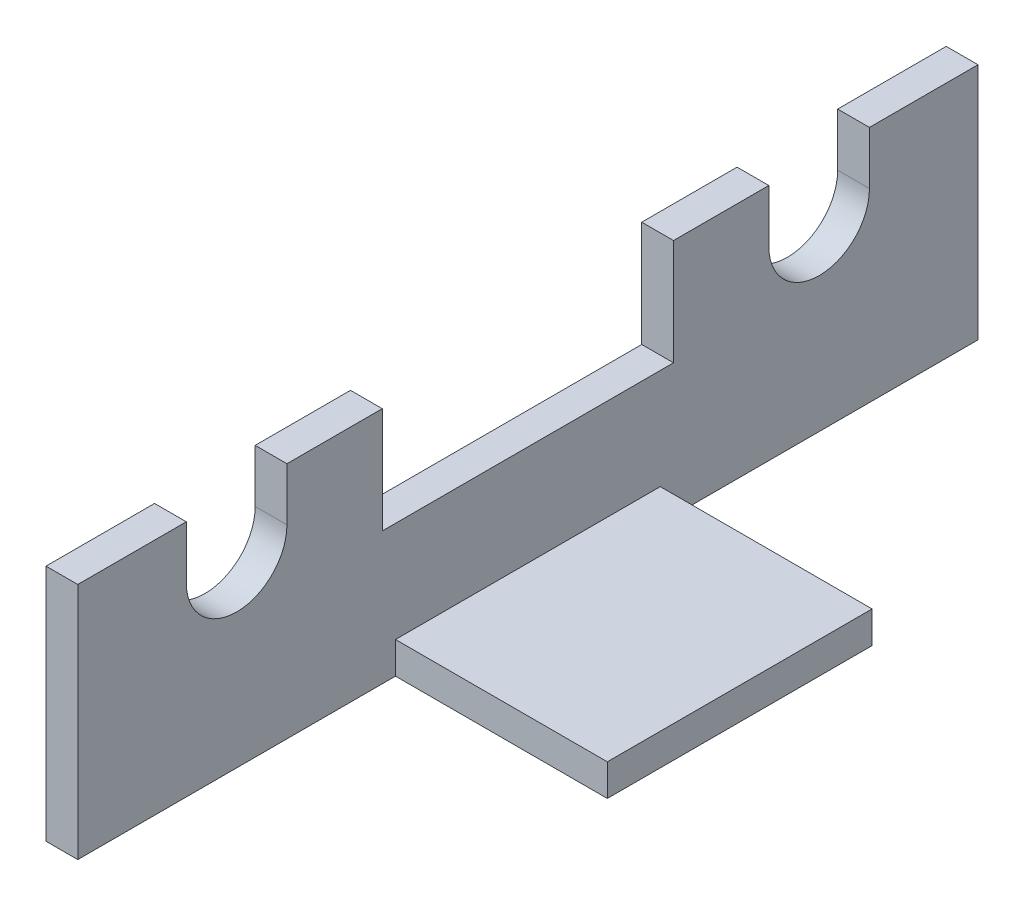
SolidWorks part; units mm, degrees
ref_plane "Alzado" through (0, 0, 0) normal (0, 0, 1) x (1, 0, 0)
ref_plane "Planta" through (0, 0, 0) normal (0, 1, 0) x (1, 0, 0)
ref_plane "Vista lateral" through (0, 0, 0) normal (1, 0, 0) x (0, 0, -1)
sketch "Croquis1" plane through (0, 0, 0) normal (0, 0, 1) x (1, 0, 0)
  line L0 (0, 0) -> (0, 50)
  line L1 (0, 0) -> (50, 0)
  line L2 (6, 6) -> (50, 6)
  line L3 (6, 6) -> (6, 50)
  line L4 (0, 50) -> (6, 50)
  line L5 (50, 6) -> (50, 0)
  dimension "D2" = 50
  dimension "D1" = 6
extrude "Saliente-Extruir1" add sketch "Croquis1" along normal blind 170
sketch "Croquis2" plane through (0, 0, 0) normal (-1, 0, 0) x (0, 0, 1)
  line L0 (170, 35) -> (0, 35) construction
  line L1 (170, 50) -> (170, 0) construction
  line L2 (0, 50) -> (0, 0) construction
  line L3 (170, 6) -> (0, 6) construction
  line L4 (170, 6) -> (0, 6) construction
  line L5 (85, 6) -> (85, 50) construction
  line L6 (170, 50) -> (0, 50) construction
  line L7 (112.5, 25) -> (112.5, 50)
  line L8 (112.5, 75) -> (57.5, 75) construction
  line L9 (112.5, 75) -> (112.5, 25) construction
  line L10 (112.5, 25) -> (57.5, 25)
  line L11 (57.5, 75) -> (57.5, 25) construction
  line L12 (112.5, 75) -> (57.5, 25) construction
  line L13 (112.5, 25) -> (57.5, 75) construction
  line L14 (57.5, 25) -> (57.5, 50)
  line L15 (57.5, 50) -> (112.5, 50)
  line L16 (149.5, 35) -> (149.5, 50)
  line L17 (130.5, 35) -> (130.5, 50)
  line L18 (130.5, 50) -> (149.5, 50)
  line L19 (39.5, 35) -> (39.5, 50)
  line L20 (20.5, 35) -> (20.5, 50)
  line L21 (39.5, 50) -> (20.5, 50)
  line L22 (170, 0) -> (0, 0) construction
  circle A0 centre (140, 35) radius 9.5 construction
  circle A1 centre (30, 35) radius 9.5 construction
  arc A2 (149.5, 35) -> (130.5, 35) centre (140, 35) cw
  arc A3 (39.5, 35) -> (20.5, 35) centre (30, 35) cw
  dimension "D2" = 19
  dimension "D1" = 35
  dimension "D3" = 55
  dimension "D4" = 55
  dimension "D5" = 25
  dimension "D6" = 55
  dimension "D7" = 20.5
  dimension "D8" = 20.5
extrude "Cortar-Extruir1" cut sketch "Croquis2" against normal up to surface (6 mm away) up to face at (6, 28, 85)
sketch "Croquis3" plane through (0, 0, 0) normal (0, -1, 0) x (1, 0, 0)
  line L0 (0, 85) -> (50, 85) construction
  line L1 (0, 170) -> (0, 0) construction
  line L2 (50, 170) -> (50, 0) construction
  line L3 (6, 170) -> (6, 0) construction
  line L4 (50, 0) -> (6, 0)
  line L5 (50, 0) -> (50, 60)
  line L6 (50, 60) -> (6, 60)
  line L7 (6, 0) -> (6, 60)
  line L8 (6, 170) -> (6, 0) construction
  line L9 (50, 110) -> (6, 110)
  line L10 (6, 170) -> (6, 110)
  line L11 (50, 170) -> (6, 170)
  line L12 (50, 170) -> (50, 110)
  line M5 (0, 0) -> (50, 0)
  line M6 (50, 0) -> (50, 170)
  line M7 (50, 170) -> (0, 170)
  dimension "D1" = 60
extrude "Cortar-Extruir2" cut sketch "Croquis3" against normal up to surface (6 mm away) contours L10 L9 M7 M6 | L7 L6 M5 M6 region at (28, 0, 140) region at (28, 0, 30) up to face at (28, 6, 85)
sketch "Croquis4" plane through (0, 0, 0) normal (0, -1, 0) x (1, 0, 0)
  line L0 (46, 60) -> (46, 110)
  line L1 (50, 60) -> (6, 60) construction
  line L2 (50, 110) -> (6, 110) construction
  line L3 (46, 110) -> (50, 110)
  line L4 (50, 110) -> (50, 60)
  line L5 (50, 60) -> (46, 60)
  dimension "D1" = 4
extrude "Cortar-Extruir3" cut sketch "Croquis4" against normal blind 10
sketch "Croquis5" plane through (0, 0, 0) normal (-1, 0, 0) x (0, 0, 1)
  line L0 (170, 45) -> (0, 45) construction
  line L1 (170, 50) -> (170, 0) construction
  line L2 (0, 50) -> (0, 0) construction
  line L3 (170, 50) -> (149.5, 50) construction
  line L4 (170, 45) -> (149.5, 45)
  line L5 (149.5, 45) -> (149.5, 50)
  line L6 (149.5, 50) -> (170, 50)
  line L7 (170, 50) -> (170, 45)
  line L8 (149.5, 35) -> (149.5, 50) construction
  line L9 (112.5, 50) -> (112.5, 45)
  line L10 (112.5, 25) -> (112.5, 50) construction
  line L11 (112.5, 45) -> (130.5, 45)
  line L12 (130.5, 50) -> (130.5, 35) construction
  line L13 (130.5, 45) -> (130.5, 50)
  line L14 (130.5, 50) -> (112.5, 50)
  line L15 (85, 25) -> (85, 45) construction
  line L16 (57.5, 25) -> (112.5, 25) construction
  line L17 (39.5, 45) -> (39.5, 50)
  line L18 (57.5, 45) -> (39.5, 45)
  line L19 (57.5, 50) -> (57.5, 45)
  line L20 (39.5, 50) -> (57.5, 50)
  line L21 (20.5, 50) -> (0, 50)
  line L22 (20.5, 45) -> (20.5, 50)
  line L23 (0, 45) -> (20.5, 45)
  line L24 (0, 50) -> (0, 45)
  dimension "D1" = 5
extrude "Cortar-Extruir4" cut sketch "Croquis5" against normal up to surface (6 mm away) up to face at (6, 29.15, 85)
